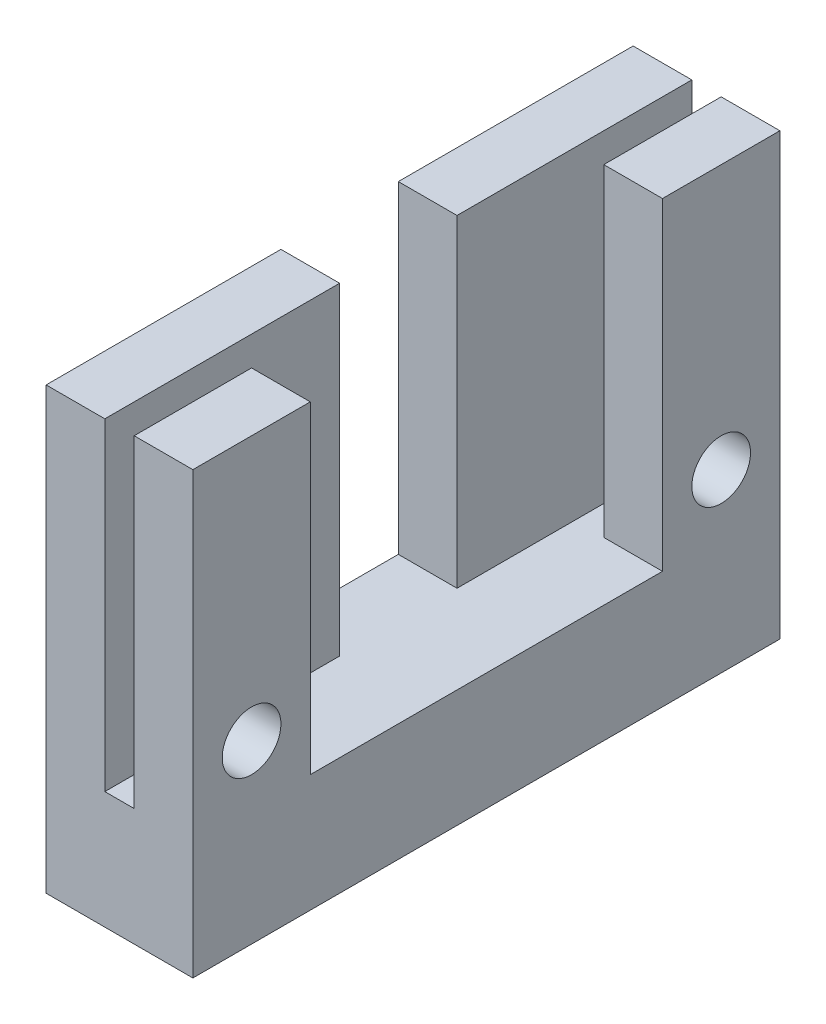
SolidWorks part; units mm, degrees
ref_plane "Front Plane" through (0, 0, 0) normal (0, 0, 1) x (1, 0, 0)
ref_plane "Top Plane" through (0, 0, 0) normal (0, 1, 0) x (1, 0, 0)
ref_plane "Right Plane" through (0, 0, 0) normal (1, 0, 0) x (0, 0, -1)
sketch "Sketch1" plane through (0, 0, 0) normal (1, 0, 0) x (0, 0, -1)
  line L1 (-10, -7.5) -> (10, -7.5)
  line L2 (-10, -7.5) -> (-10, 7.5)
  line L3 (-10, 7.5) -> (10, 7.5)
  line L4 (10, -7.5) -> (10, 7.5)
  line L5 (-10, -7.5) -> (10, 7.5) construction
  line L6 (-10, 7.5) -> (10, -7.5) construction
  point P0 (0, 0)
  dimension "D1" = 15
  dimension "D2" = 20
extrude "Boss-Extrude1" add sketch "Sketch1" along normal blind 5
sketch "Sketch2" plane through (0, 0, 10) normal (0, 0, 1) x (1, 0, 0)
  line L0 (5, 7.5) -> (0, 7.5) construction
  line L1 (2, 7.5) -> (3, 7.5)
  line L2 (2, 7.5) -> (2, -3.5)
  line L3 (2, -3.5) -> (3, -3.5)
  line L4 (3, 7.5) -> (3, -3.5)
  line L5 (5, -7.5) -> (0, -7.5) construction
  point P8 (2.5, -7.5)
  point P9 (2.5, -3.5)
  dimension "D1" = 1
  dimension "D2" = 11
extrude "Cut-Extrude1" cut sketch "Sketch2" against normal through all
sketch "Sketch3" plane through (5, 0, 0) normal (1, 0, 0) x (0, 0, -1)
  line L0 (10, 7.5) -> (-10, 7.5) construction
  line L1 (-6, 7.5) -> (6, 7.5)
  line L2 (-6, 7.5) -> (-6, -3.5)
  line L3 (-6, -3.5) -> (6, -3.5)
  line L4 (6, 7.5) -> (6, -3.5)
  line L5 (-10, -7.5) -> (10, -7.5) construction
  point P8 (0, -7.5)
  point P9 (0, -3.5)
  dimension "D1" = 12
extrude "Cut-Extrude2" cut sketch "Sketch3" against normal up to next
sketch "Sketch4" plane through (2, 0, 0) normal (1, 0, 0) x (0, 0, -1)
  line L0 (10, 7.5) -> (-10, 7.5) construction
  line L1 (-2, 7.5) -> (2, 7.5)
  line L2 (-2, 7.5) -> (-2, -3.5)
  line L3 (-2, -3.5) -> (2, -3.5)
  line L4 (2, 7.5) -> (2, -3.5)
  line L5 (-6, -3.5) -> (6, -3.5) construction
  point P8 (0, -3.5)
  point P9 (0, -3.5)
  dimension "D1" = 4
extrude "Cut-Extrude3" cut sketch "Sketch4" against normal up to next
sketch "Sketch5" plane through (5, 0, 0) normal (1, 0, 0) x (0, 0, -1)
  line L0 (-6, 7.5) -> (-10, 7.5) construction
  circle A0 centre (-8, -1.5) radius 1
  point P2 (0, 0)
  point P3 (0, 0)
  point P6 (-8, 7.5)
  point P7 (-7.5, -1.3212)
  dimension "D1" = 2
  dimension "D2" = 2
extrude "Cut-Extrude4" cut sketch "Sketch5" against normal through all
mirror "Mirror1" about plane through (0, 0, 0) normal (0, 0, 1) of "Cut-Extrude4"
